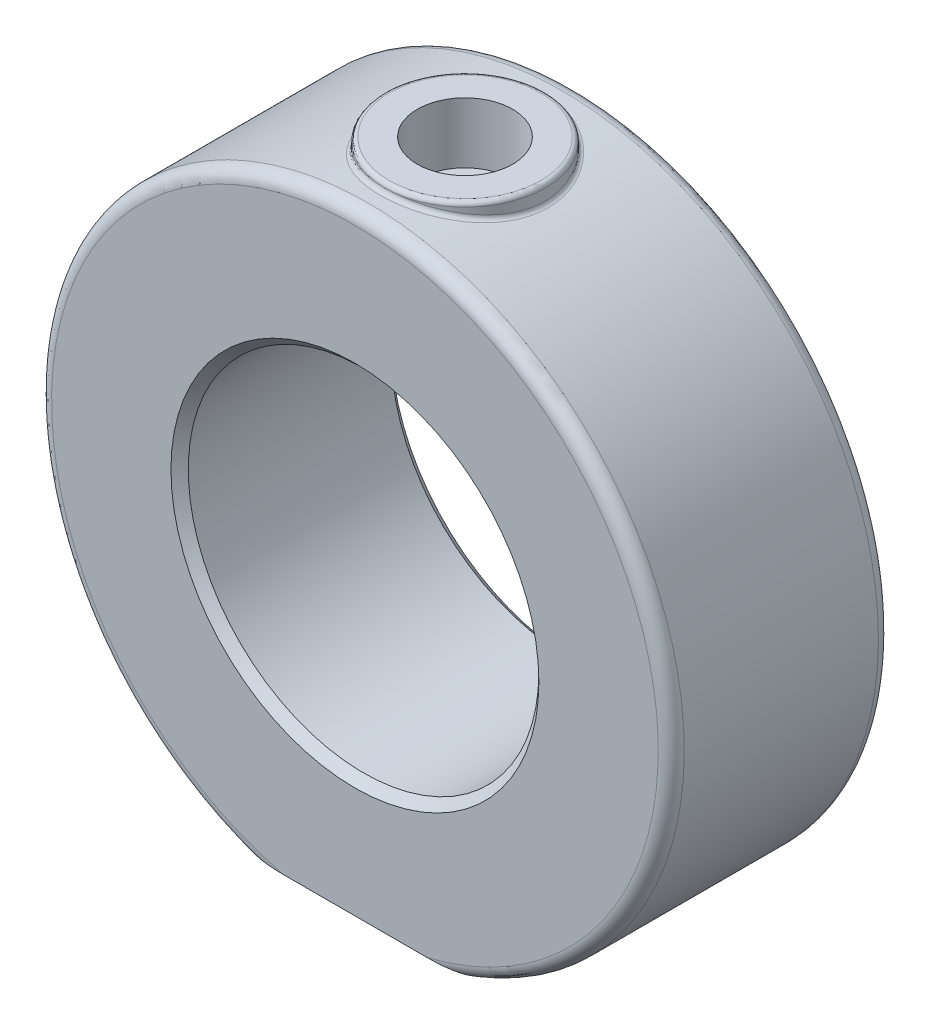
SolidWorks part; units mm, degrees
ref_plane "Front Plane" through (0, 0, 0) normal (0, 0, 1) x (1, 0, 0)
ref_plane "Top Plane" through (0, 0, 0) normal (0, 1, 0) x (1, 0, 0)
ref_plane "Right Plane" through (0, 0, 0) normal (1, 0, 0) x (0, 0, -1)
sketch "Sketch2" plane through (0, 0, 0) normal (0, 0, 1) x (1, 0, 0)
  circle A0 centre (0, 0) radius 73
  circle A1 centre (0, 0) radius 40.45
  dimension "D1" = 146
  dimension "D2" = 80.9
extrude "Boss-Extrude1" add sketch "Sketch2" along normal blind 50.8
fillet "Fillet1" radius 3 2 edges at (73, 0, 0) (73, 0, 50.8)
ref_plane "Plane1" through (0, 75, 0) normal (0, 1, 0) x (1, 0, 0)
sketch "Sketch3" plane through (0, 75, 0) normal (0, 1, 0) x (1, 0, 0)
  line L0 (0, 0) -> (0, -25.4) construction
  circle A0 centre (0, -25.4) radius 18.5
  dimension "D1" = 37
  dimension "D2" = 25.4
extrude "Boss-Extrude2" add sketch "Sketch3" against normal up to surface (2 mm away) up to face at (73, 0, 3)
fillet "Fillet2" radius 1 2 edges at (0, 75, 43.9) (-3.6011, 72.9111, 7.2539)
sketch "Sketch4" plane through (0, 75, 0) normal (0, 1, 0) x (1, 0, 0)
  circle A0 centre (0, -25.4) radius 11
  dimension "D1" = 22
extrude "Cut-Extrude1" cut sketch "Sketch4" against normal blind 14
sketch "Sketch5" plane through (0, 61, 0) normal (0, 1, 0) x (1, 0, 0)
  circle A0 centre (0, -25.4) radius 4.5
extrude "Cut-Extrude2" cut sketch "Sketch5" against normal blind 37
ref_plane "Plane2" through (0, -68, 0) normal (0, 1, 0) x (1, 0, 0)
sketch "Sketch6" plane through (0, -68, 0) normal (0, 1, 0) x (1, 0, 0)
  line L1 (-30.8189, 11.7686) -> (30.8189, 11.7686)
  line L2 (-30.8189, 11.7686) -> (-30.8189, -62.5686)
  line L3 (-30.8189, -62.5686) -> (30.8189, -62.5686)
  line L4 (30.8189, 11.7686) -> (30.8189, -62.5686)
  line L5 (-30.8189, 11.7686) -> (30.8189, -62.5686) construction
  line L6 (-30.8189, -62.5686) -> (30.8189, 11.7686) construction
  point P0 (0, -25.4)
extrude "Cut-Extrude3" cut sketch "Sketch6" against normal blind 37
sketch "Sketch7" plane through (0, -68, 0) normal (0, -1, 0) x (1, 0, 0)
  circle A0 centre (0, 25.4) radius 5
  dimension "D1" = 10
  dimension "D2" = 25.4
extrude "Cut-Extrude4" cut sketch "Sketch7" against normal blind 5
chamfer "Chamfer1" distance 2 angle 45 2 edges at (40.45, 0, 50.8) (40.45, 0, 0)
ref_plane "Plane3" through (-68, 0, 0) normal (1, 0, 0) x (0, 0, -1)
sketch "Sketch8" plane through (-68, 0, 0) normal (1, 0, 0) x (0, 0, -1)
  line L1 (0, -68) -> (0, 70) construction
  circle A0 centre (-25.4, -32) radius 18
  dimension "D1" = 36
  dimension "D2" = 32
  dimension "D3" = 25.4
extrude "Boss-Extrude3" add sketch "Sketch8" along normal up to next
fillet "Fillet3" radius 1 3 edges at (-68, -26.5518, 25.4) (-53.2439, -49.9408, 23.9419) (-68, -50, 25.4)
